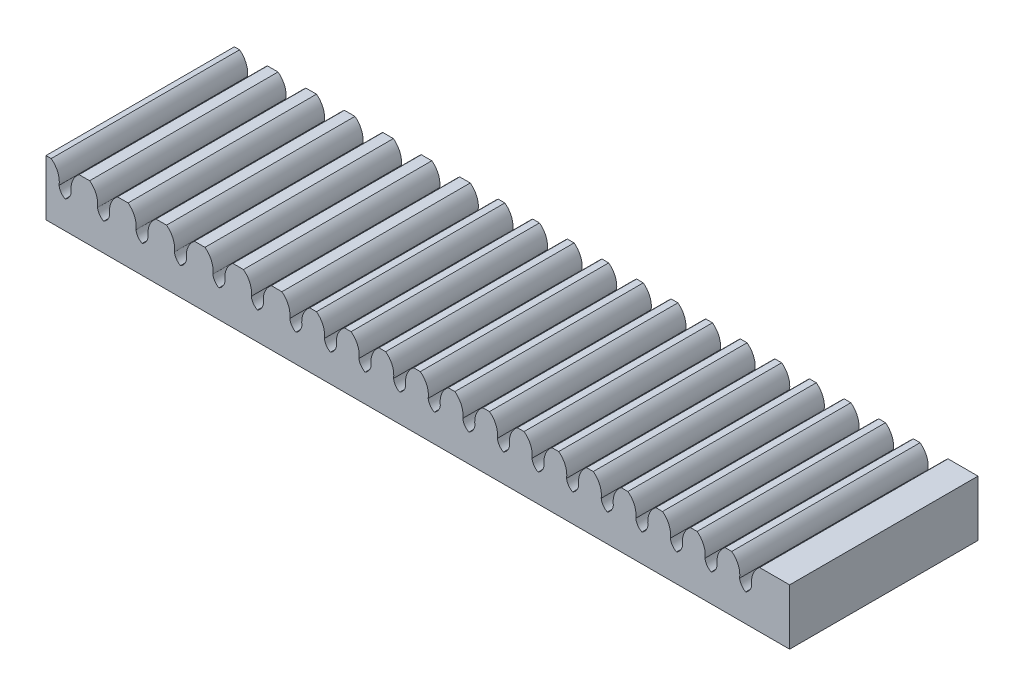
SolidWorks part; units mm, degrees
ref_plane "Front Plane" through (0, 0, 0) normal (0, 0, 1) x (1, 0, 0)
ref_plane "Top Plane" through (0, 0, 0) normal (0, 1, 0) x (1, 0, 0)
ref_plane "Right Plane" through (0, 0, 0) normal (1, 0, 0) x (0, 0, -1)
sketch "Sketch1" plane through (0, 0, 0) normal (0, 0, 1) x (1, 0, 0)
  line L0 (28, 7) -> (-39.3732, 7)
  line L1 (-39.3732, 7) -> (-39.3732, -0.2491)
  line L2 (-39.3732, -0.2491) -> (0.9392, -0.2491)
  line L3 (0.9392, -0.2491) -> (57.3333, -0.2491)
  line L4 (57.3333, -0.2491) -> (57.3333, 7)
  line L5 (57.3333, 7) -> (28, 7)
  point P0 (57.3333, 3.3754)
  dimension "D1" = 96.7065
extrude "Boss-Extrude1" add sketch "Sketch1" along normal blind 24.5
sketch "Sketch2" plane through (0, 0, 0) normal (0, 0, 1) x (1, 0, 0)
  line L0 (-6.8813, 0.8955) -> (-6.8813, 9.6802) construction
  arc A5 (-6.8813, 3.3484) -> (-7.6713, 4.4984) centre (-6.1725, 4.6817) cw
  arc A12 (-7.6713, 4.4984) -> (-8.9813, 7.188) centre (-10.3038, 4.8801) ccw
  arc A13 (-6.0913, 4.4984) -> (-4.7813, 7.188) centre (-3.4588, 4.8801) cw
  arc A14 (-6.8813, 3.3484) -> (-6.0913, 4.4984) centre (-7.5901, 4.6817) ccw
  arc A15 (-8.9813, 7.188) -> (-4.7813, 7.188) centre (-6.8813, 3.6353) cw
  dimension "D4" = 2.66
  dimension "D5" = 1.51
  dimension "D6" = 1.15
  dimension "D8" = 2.1
  dimension "D10" = 0.79
extrude "Cut-Extrude1" cut sketch "Sketch2" along normal blind 26.12
pattern_linear "LPattern1" count 10 spacing 5 along (-1, 0, 0) count 14 spacing 4.5 along (1, 0, 0) of "Cut-Extrude1" pattern seed only yes
